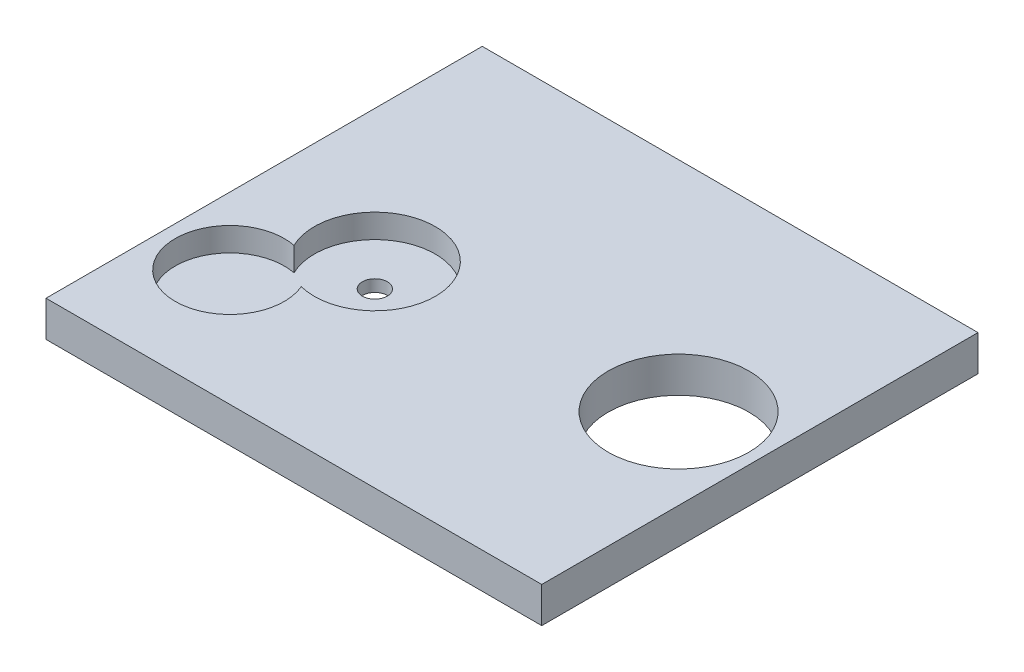
SolidWorks part; units mm, degrees
ref_plane "Front" through (0, 0, 0) normal (0, 0, 1) x (1, 0, 0)
ref_plane "Top" through (0, 0, 0) normal (0, 1, 0) x (1, 0, 0)
ref_plane "Right" through (0, 0, 0) normal (1, 0, 0) x (0, 0, -1)
sketch "Sketch1" plane through (0, 0, 0) normal (0, 1, 0) x (1, 0, 0)
  line L1 (0, 0) -> (125, 0)
  line L2 (0, 0) -> (0, 110)
  line L3 (0, 110) -> (125, 110)
  line L4 (125, 0) -> (125, 110)
  dimension "D1" = 125
  dimension "D2" = 110
extrude "Top_Base" add sketch "Sketch1" along normal blind 9
sketch "Fingers_Position" plane through (0, 9, 0) normal (0, 1, 0) x (1, 0, 0)
  line L0 (74.5, 89.5) -> (39.5, 89.5) construction
  line L1 (74.5, 73.5) -> (19.5, 73.5) construction
  line L2 (74.5, 73.5) -> (74.5, 105.5) construction
  line L3 (74.5, 105.5) -> (19.5, 105.5) construction
  line L4 (19.5, 73.5) -> (19.5, 105.5) construction
  line L5 (74.5, 4.5) -> (19.5, 4.5) construction
  line L6 (74.5, 4.5) -> (74.5, 36.5) construction
  line L7 (74.5, 36.5) -> (19.5, 36.5) construction
  line L8 (19.5, 4.5) -> (19.5, 36.5) construction
  line L10 (39.5, 20.5) -> (74.5, 20.5) construction
  line L11 (125, 110) -> (0, 110) construction
  line L12 (0, 110) -> (0, 0) construction
  dimension "D1" = 55
  dimension "D2" = 32
  dimension "D3" = 69
  dimension "D4" = 4.5
  dimension "D5" = 19.5
  dimension "D6" = 20
sketch "Intermediate_Gear_Position" plane through (0, 9, 0) normal (0, 1, 0) x (1, 0, 0)
  line L0 (0, 49.485) -> (33.4314, 49.485) construction
  line L1 (0, 110) -> (0, 0) construction
  line L2 (33.4314, 49.485) -> (33.4314, 110) construction
  line L3 (125, 110) -> (0, 110) construction
  line L4 (33.4314, 49.485) -> (33.4314, 0) construction
  line L5 (0, 0) -> (125, 0) construction
  circle A0 centre (33.4314, 49.485) radius 15 construction
  circle A1 centre (33.4314, 49.485) radius 13.5
  circle A2 centre (33.4314, 49.485) radius 13.75 construction
  dimension "D3" = 30
  dimension "D4" = 27
  dimension "D5" = 27.5
  dimension "D1" = 33.4314
  dimension "D2" = 49.485
sketch "Drive_Gear_Position" plane through (0, 9, 0) normal (0, 1, 0) x (1, 0, 0)
  line L0 (5, 20.3354) -> (29, 20.3354) construction
  line L1 (5, 38.3354) -> (29, 38.3354)
  line L2 (5, 38.3354) -> (5, 2.3354)
  line L3 (5, 2.3354) -> (29, 2.3354)
  line L4 (29, 38.3354) -> (29, 2.3354)
  line L5 (17, 38.3354) -> (17, 2.3354) construction
  line L6 (95.5, 98) -> (95.5, 43) construction
  line L7 (79.5, 98) -> (111.5, 98) construction
  line L8 (79.5, 98) -> (79.5, 43) construction
  line L9 (79.5, 43) -> (111.5, 43) construction
  line L10 (111.5, 98) -> (111.5, 43) construction
  line L11 (77.5, 67) -> (113.5, 67) construction
  line L12 (77.5, 67) -> (77.5, 43) construction
  line L13 (77.5, 43) -> (113.5, 43) construction
  line L14 (113.5, 67) -> (113.5, 43) construction
  line L15 (95.5, 67) -> (95.5, 43) construction
  line L17 (125, 0) -> (125, 110) construction
  line L18 (125, 110) -> (0, 110) construction
  line L20 (0, 110) -> (0, 0) construction
  circle A0 centre (17, 29.3354) radius 9 construction
  circle A1 centre (17, 29.3354) radius 13.5 construction
  circle A2 centre (17, 29.3354) radius 12
  circle A4 centre (17, 29.3354) radius 12.25 construction
  circle A5 centre (33.4314, 49.485) radius 13.75 construction
  dimension "D1" = 27
  dimension "D2" = 18
  dimension "D5" = 24
  dimension "D13" = 24.5
  dimension "D3" = 24
  dimension "D4" = 36
  dimension "D6" = 32
  dimension "D7" = 55
  dimension "D8" = 24
  dimension "D9" = 36
  dimension "D10" = 13.5
  dimension "D11" = 12
  dimension "D12" = 5
sketch "Sketch5" plane through (0, 9, 0) normal (0, 1, 0) x (1, 0, 0)
  circle A0 centre (33.4314, 49.485) radius 15.25
  circle A1 centre (17, 29.3354) radius 13.75
  dimension "D1" = 27.5
  dimension "D2" = 30.5
extrude "Gears_Extrude_Cut" cut sketch "Sketch5" against normal blind 6 contours A0 A1 | A1 A0 | A0 A1 region at (33.7515, 9, -49.8776) region at (24.7317, 9, -38.8166) region at (16.6471, 9, -28.9026)
sketch "Sketch7" plane through (0, 9, 0) normal (0, 1, 0) x (1, 0, 0)
  circle A0 centre (33.4314, 49.485) radius 3.15
  dimension "D1" = 6.3
extrude "Key_Extrude_Cut" cut sketch "Sketch7" against normal through all
sketch "Sketch8" plane through (0, 9, 0) normal (0, 1, 0) x (1, 0, 0)
  line L0 (113.5, 55) -> (77.5, 55) construction
  line L1 (113.5, 67) -> (113.5, 43) construction
  line L2 (77.5, 67) -> (77.5, 43) construction
  circle A0 centre (104.5, 55) radius 9 construction
  circle A1 centre (104.5, 55) radius 17.75
  dimension "D1" = 18
  dimension "D2" = 35.5
extrude "Cut-Extrude3" cut sketch "Sketch8" against normal through all
